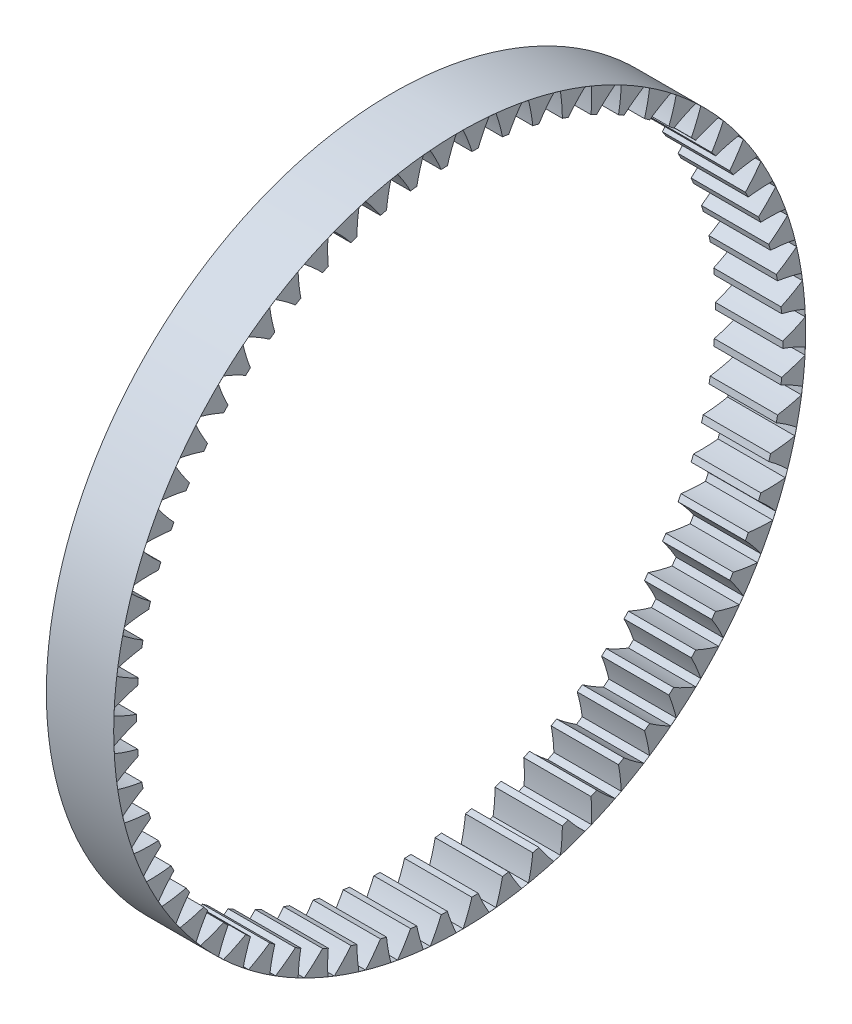
SolidWorks part; units mm, degrees
ref_plane "Plane1" through (0, 0, 0) normal (0, 0, 1) x (1, 0, 0)
ref_plane "Plane2" through (0, 0, 0) normal (0, 1, 0) x (1, 0, 0)
ref_plane "Plane3" through (0, 0, 0) normal (1, 0, 0) x (0, 0, -1)
sketch "HoldingSke" plane through (0, 0, 0) normal (0, 1, 0) x (1, 0, 0)
  line L0 (0, 0) -> (0.1808, -0.406)
  line L1 (-15, 0) -> (100, 0) construction
  line L2 (0, 0) -> (-2.1039, 2.3779)
  line L3 (0, 0) -> (-11.863, 4.5341)
  line L4 (0, 0) -> (3.5126, 7.8894)
  line L5 (0, 0) -> (-23.7986, -8.8762)
  line L6 (0, 0) -> (-10.5278, -7.1032)
  line L7 (-2.1039, 2.3779) -> (3.3635, 27.1825)
  line L8 (-76.2, 4.6279) -> (-54.61, 4.6279)
  line L9 (-71.009, 38.7566) -> (-53.1078, 45.2721)
  line L10 (-76.2, 71.12) -> (104.1128, 71.12)
  line L11 (0, 0) -> (-15, 0)
  line L12 (-76.2, 101.6) -> (-76.123, 101.6)
  line L13 (24.9733, 27.94) -> (52.9518, 28.4284)
  line L14 (24.9733, 27.94) -> (24.9743, 27.94)
  line L15 (24.9733, 27.94) -> (100.4006, 29.5858)
  circle A0 centre (0, 0) radius 75
  circle A1 centre (0, 0) radius 12.7
  circle A2 centre (0, 0) radius 12.7
  dimension "Num_teeth" = 66
  dimension "Pitch_radius" = 180.3128
  dimension "Width" = 15
sketch "BasProSke" plane through (0, 0, 0) normal (0, 1, 0) x (1, 0, 0)
  line L0 (-10, 0) -> (60, 0) construction
  line L1 (0, 72) -> (0, 77.0889)
  line L2 (0, 72) -> (15, 72)
  line L3 (15, 72) -> (15, 77.0889)
  line L4 (15, 77.0889) -> (0, 77.0889)
  dimension "Thickness" = 15
  dimension "Diameter" = 154.1778
revolve "Base-Revolve" add sketch "BasProSke" angle 360 about L0
sketch "TooCutSke" plane through (0, 0, 0) normal (1, 0, 0) x (0, 0, -1)
  line L3 (1.9595, 74.2241) -> (1.9595, 53.6633) construction
  line L4 (0, 0) -> (0, 59.563) construction
  line L5 (0, 0) -> (-3.2512, 68.2501) construction
  line L6 (-32.8439, 61.3016) -> (34.812, 64.5245) construction
  circle A0 centre (0, 0) radius 74.25 construction
  circle A1 centre (0, 0) radius 77.0635 construction
  circle A2 centre (0, 0) radius 62.795 construction
  circle A3 centre (0, 0) radius 71.9746 construction
  arc A4 (2.7294, 71.9228) -> (0.7708, 77.0596) centre (-32.8439, 61.3016) ccw
  arc A5 (2.7294, 71.9228) -> (-2.7294, 71.9228) centre (0, 0) ccw
  arc A6 (0.7708, 77.0596) -> (-0.7708, 77.0596) centre (0, 0) ccw
  arc A7 (-0.7708, 77.0596) -> (-2.7294, 71.9228) centre (32.8439, 61.3016) ccw
extrude "ToothCut" cut sketch "TooCutSke" along normal through all
fillet "Breaks" [suppressed] radius 0.225
fillet "RootFillets" [suppressed] radius 0.5635
pattern_circular "TeethCuts" count 66 every 5.455 about axis through (-10, 0, 0) along (1, 0, 0) of "RootFillets", "Breaks", "ToothCut"
equation "' \"Module@HoldingSke\" = 6.35"
equation "' \"Num_teeth@HoldingSke\" = 24"
equation "' \"Ap@HoldingSke\" =  14.5"
equation "' \"Ap@HoldingSke\" = 14.5"
equation "' \"Width@HoldingSke\" = 12"
equation "' \"Diameter@HoldingSke\" = 8 * 25.4"
equation "' \"Show_teeth@HoldingSke\" = 100"
equation "' \"Backlash@HoldingSke\" = 0.009 * 25.4"
equation "' \"Addendum_fac@HoldingSke\" = 1.0"
equation "' \"Dedendum_fac@HoldingSke\" = 1.25"
equation "' \"Dedendum_add@HoldingSke\" = 0.00005 * 25.4"
equation "' \"Clearance_fac@HoldingSke\" = 0.25"
equation "\"Pitch@HoldingSke\" = 1 / \"Module@HoldingSke\" "
equation "\"Overcut_dia@TooCutSke\" = (\"Num_teeth@HoldingSke\" - 2 * \"Addendum_fac@HoldingSke\") / \"Pitch@HoldingSke\" - 0.002 * 25.4"
equation "\"Pitch_dia@TooCutSke\" = \"Num_teeth@HoldingSke\" / \"Pitch@HoldingSke\""
equation "\"Base_dia@TooCutSke\" = \"Num_teeth@HoldingSke\" / \"Pitch@HoldingSke\" * cos((\"Ap@HoldingSke\"  * 3.14159265 / 180)) * 0.90"
equation "\"Root_dia@TooCutSke\" = \"Num_teeth@HoldingSke\"  / \"Pitch@HoldingSke\" + 2 *  \"Dedendum_fac@HoldingSke\"/ \"Pitch@HoldingSke\" + \"Dedendum_add@HoldingSke\" * 2"
equation "\"Half_ang@TooCutSke\" = 180 / \"Num_teeth@HoldingSke\""
equation "\"Half_CT@TooCutSke\" = \"Num_teeth@HoldingSke\" / \"Pitch@HoldingSke\" * sin((3.14159265 / 2 / \"Num_teeth@HoldingSke\")) / 2 + 10 * \"Backlash@HoldingSke\" / 4"
equation "\"Flank_rad@TooCutSke\" = \"Num_teeth@HoldingSke\" / \"Pitch@HoldingSke\" / 4"
equation "\"Radius@RootFillets\"= \"Clearance_fac@HoldingSke\" / \"Pitch@HoldingSke\" + \"Dedendum_add@HoldingSke\""
equation "\"Break_rad@Breaks\" = 0.02 / \"Pitch@HoldingSke\" * 5"
equation "\"Num_teeth@TeethCuts\" = int( \"Show_teeth@HoldingSke\" ) + 1"
equation "\"Num_teeth@TeethCuts\" = ((sgn( \"Num_teeth@TeethCuts\" - \"Num_teeth@HoldingSke\" )-1)*( \"Num_teeth@TeethCuts\" - \"Num_teeth@HoldingSke\" ))/-2+ \"Num_teeth@HoldingSke\""
equation "\"Num_teeth@TeethCuts\" = ((sgn( \"Num_teeth@TeethCuts\" - 2.0)+1)*( \"Num_teeth@TeethCuts\" - 2.0))/2 +2.0"
equation "\"Angle@TeethCuts\" = 360.0 / \"Num_teeth@HoldingSke\""
equation "\"Diameter@BasProSke\" = \"Num_teeth@HoldingSke\"  / \"Pitch@HoldingSke\" + 2 *  \"Dedendum_fac@HoldingSke\"/ \"Pitch@HoldingSke\" + \"Dedendum_add@HoldingSke\" * 2 + 0.002 * 25.4"
equation "\"Diameter@BasProSke\" = ((sgn( \"Diameter@BasProSke\"  - \"Diameter@HoldingSke\" )+1)*( \"Diameter@BasProSke\"  - \"Diameter@HoldingSke\" ))/2 + \"Diameter@HoldingSke\""
equation "\"Inside_diameter@BasProSke\" =  (\"Num_teeth@HoldingSke\" - 2 * \"Addendum_fac@HoldingSke\") / \"Pitch@HoldingSke\" "
equation "\"Thickness@BasProSke\"  = \"Width@HoldingSke\""
